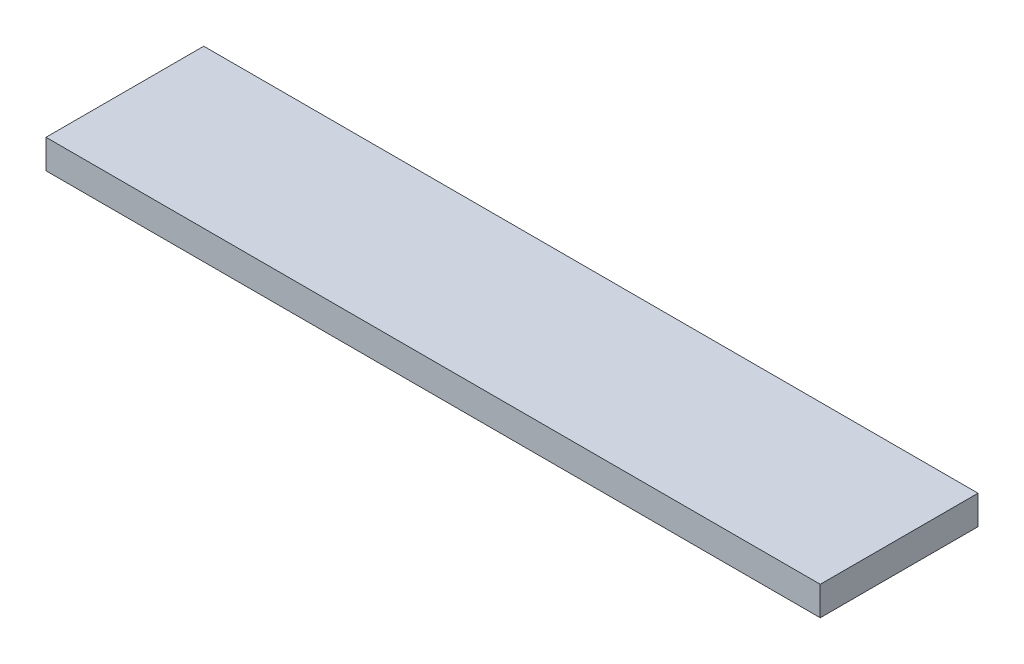
SolidWorks part; units mm, degrees
ref_plane "Front Plane" through (0, 0, 0) normal (0, 0, 1) x (1, 0, 0)
ref_plane "Top Plane" through (0, 0, 0) normal (0, 1, 0) x (1, 0, 0)
ref_plane "Right Plane" through (0, 0, 0) normal (1, 0, 0) x (0, 0, -1)
sketch "Sketch1" plane through (0, 0, 0) normal (0, 1, 0) x (1, 0, 0)
  line L1 (0, 0) -> (80, 0)
  line L2 (0, 0) -> (0, -16.3)
  line L3 (0, -16.3) -> (80, -16.3)
  line L4 (80, 0) -> (80, -16.3)
sketch "Sketch2" plane through (0, 0, 0) normal (1, 0, 0) x (0, 0, -1)
  line L1 (0, 0) -> (-16.3, 0)
  line L2 (0, 0) -> (0, -3)
  line L3 (0, -3) -> (-16.3, -3)
  line L4 (-16.3, 0) -> (-16.3, -3)
extrude "Boss-Extrude1" add sketch "Sketch1" against normal up to vertex (3 mm away) up to point (0, -3, 0)
